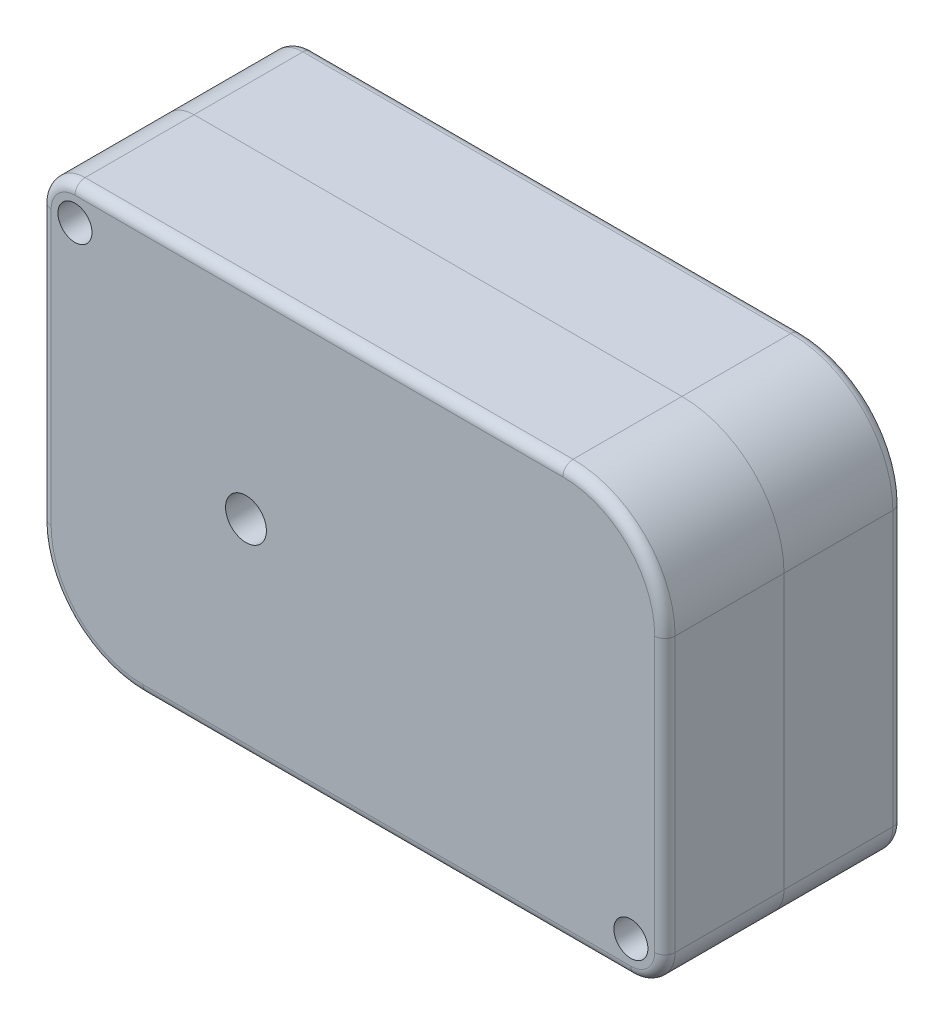
SolidWorks part; units mm, degrees
ref_plane "Front Plane" through (0, 0, 0) normal (0, 0, 1) x (1, 0, 0)
ref_plane "Top Plane" through (0, 0, 0) normal (0, 1, 0) x (1, 0, 0)
ref_plane "Right Plane" through (0, 0, 0) normal (1, 0, 0) x (0, 0, -1)
sketch "Sketch1" plane through (0, 0, 0) normal (0, 0, 1) x (1, 0, 0)
  line L0 (-91.0423, 53.272) -> (28.1923, 53.272)
  line L1 (-113.122, 60.272) -> (30.272, 60.272)
  line L2 (-123.122, 50.272) -> (-123.122, -30.272)
  line L3 (-93.122, -60.272) -> (50.272, -60.272)
  line L4 (60.272, 30.272) -> (60.272, -50.272)
  line L5 (-91.0423, -53.272) -> (28.1923, -53.272)
  line L6 (-116.122, -28.1923) -> (-116.122, 28.1923)
  line L7 (53.272, -28.1923) -> (53.272, 28.1923)
  arc A1 (-31.425, -39.2396) -> (-31.425, 39.2396) centre (0, 0) ccw
  arc A5 (-15.0759, 15.6496) -> (-15.0759, -15.6496) centre (-62.85, 0) ccw
  arc A6 (-62.85, 60.272) -> (-62.85, -60.272) centre (-62.85, 0) ccw
  arc A7 (0, -60.272) -> (0, 60.272) centre (0, 0) ccw
  arc A8 (50.272, -60.272) -> (60.272, -50.272) centre (50.272, -50.272) ccw
  arc A11 (-113.122, 60.272) -> (-123.122, 50.272) centre (-113.122, 50.272) ccw
  arc A12 (-12.6047, 17.7007) -> (-12.6047, -17.7007) centre (-62.85, 0) ccw
  arc A13 (-31.425, -43.016) -> (-31.425, 43.016) centre (0, 0) ccw
  arc A14 (-31.425, 51.4313) -> (-31.425, -51.4313) centre (-62.85, 0) ccw construction
  arc A15 (-31.425, -51.4313) -> (-31.425, 51.4313) centre (0, 0) ccw construction
  arc A16 (30.272, 60.272) -> (60.272, 30.272) centre (30.272, 30.272) cw
  arc A17 (-123.122, -30.272) -> (-93.122, -60.272) centre (-93.122, -30.272) ccw
  circle A18 centre (-113.122, 50.272) radius 5
  circle A19 centre (50.272, -50.272) radius 5
  circle A20 centre (0, 0) radius 15.73
  circle A21 centre (0, 0) radius 21.73
  arc A22 (-31.425, 39.2396) -> (-31.425, -39.2396) centre (-62.85, 0) ccw construction
  arc A23 (-31.425, 43.016) -> (-31.425, -43.016) centre (-62.85, 0) ccw construction
  point P5 (0, 0)
  point P6 (0, 0)
  point P40 (53.272, 0)
  point P50 (-116.122, 0)
  dimension "D3" = 100.544
  dimension "D1" = 100.544
  dimension "D5" = 10
  dimension "D6" = 10
  dimension "D8" = 30
  dimension "D9" = 10
  dimension "D10" = 10
  dimension "D11" = 31.46
  dimension "D2" = 62.85
  dimension "D12" = 6
  dimension "D4" = 10
  dimension "D7" = 3
extrude "Boss-Extrude1" add sketch "Sketch1" along normal blind 25 contours L1 A11 L2 A6 A18 | A16 L1 A7 L4 | L3 A8 L4 A7 A19 | L2 A17 L3 A6 | L0 A7 L1 A6 | L3 A7 L5 A6 | L6 A6 | A7 L7 region at (-31.425, 56.5135, 0) region at (-108.9044, 46.0544, 0) region at (-118.9364, 0, 0) region at (44.5822, 44.5822, 0) region at (-107.4322, -44.5822, 0) region at (56.0864, 0, 0) region at (-31.425, -56.5135, 0) region at (46.0544, -46.0544, 0)
extrude "Boss-Extrude5" add sketch "Sketch1<5>" along normal blind 15 contours A21 A12 A1 | A13 A12 A1 | A13 L0 A12 | A13 L7 A7 L0 | A13 L5 A7 L7 | A13 A12 L5 | A12 L6 A6 L5 | A12 L0 A6 L6 region at (-101.133, 38.283, 0) region at (-31.425, 50.2536, 0) region at (38.283, 38.283, 0) region at (36.7066, 36.7066, 0) region at (-101.133, -38.283, 0) region at (38.283, -38.283, 0) region at (48.9919, 0, 0) region at (-31.425, -50.2536, 0)
sketch "Sketch1<5>" plane through (0, 0, 0) normal (0, 0, 1) x (1, 0, 0) same geometry as "Sketch1"
extrude "Boss-Extrude2" add sketch "Sketch1<3>" against normal blind 10 contours L1 A11 L2 A6 A18 | L0 A7 L1 A6 | A12 L0 A6 L6 | L6 A6 | A12 L6 A6 L5 | L2 A17 L3 A6 | A1 A12 A5 | A21 A5 | L3 A7 L5 A6 | A13 A12 L5 | A21 A5 A1 A12 | A20 | A21 A12 A1 A5 | A21 A20 | A21 A12 A1 | A13 A12 A1 | A13 L0 A12 | A13 L7 A7 L0 | A16 L1 A7 L4 | A7 L7 | L3 A8 L4 A7 A19 | A13 L5 A7 L7 region at (-31.425, 56.5135, 0) region at (-108.9044, 46.0544, 0) region at (-101.133, 38.283, 0) region at (-31.425, 50.2536, 0) region at (-46.749, 49.3345, 0) region at (-118.9364, 0, 0) region at (38.283, 38.283, 0) region at (36.7066, 36.7066, 0) region at (-101.133, -38.283, 0) region at (44.5822, 44.5822, 0) region at (-107.4322, -44.5822, 0) region at (56.0864, 0, 0) region at (38.283, -38.283, 0) region at (-20.9278, 29.2135, 0) region at (48.9919, 0, 0) region at (-31.425, -56.5135, 0) region at (-31.425, -50.2536, 0) region at (46.0544, -46.0544, 0) region at (-20.9278, -29.2135, 0) region at (-64.0167, 0, 0) region at (9.6756, 18.7681, 0) region at (0, 0, 0)
sketch "Sketch1<3>" plane through (0, 0, 0) normal (0, 0, 1) x (1, 0, 0) same geometry as "Sketch1"
fillet "Fillet1" radius 3 8 edges at (-21.425, -60.272, -10) (57.3431, -57.3431, -10) (60.272, -10, -10) (51.4852, 51.4852, -10) (-41.425, 60.272, -10) (-120.1931, 57.3431, -10) (-123.122, 10, -10) (-114.3352, -51.4852, -10)
ref_plane "Plane1" through (0, 0, 25) normal (0, 0, 1) x (1, 0, 0)
mirror "Mirror1" about plane through (0, 0, 25) normal (0, 0, 1) of bodies 115 109
sketch "Sketch2" plane through (0, 0, -10) normal (0, 0, -1) x (-1, 0, 0)
  circle A0 centre (62.85, 0) radius 6
  circle A1 centre (62.85, 0) radius 50
  dimension "D1" = 12
  dimension "D2" = 100
extrude "Boss-Extrude6" add sketch "Sketch2" along normal blind 5 contours A1 A0 region at (-14.2642, 0, -10)
extrude "Cut-Extrude1" cut sketch "Sketch2<3>" against normal through all contours A0 region at (-62.85, 0, -10)
sketch "Sketch2<3>" plane through (0, 0, -10) normal (0, 0, -1) x (-1, 0, 0) same geometry as "Sketch2"
sketch "Sketch3" plane through (0, 0, -15) normal (0, 0, -1) x (-1, 0, 0)
  circle A0 centre (62.85, 0) radius 35 construction
  circle A1 centre (62.85, 35) radius 2.5
  circle A2 centre (87.5987, 24.7487) radius 2.5
  circle A3 centre (97.85, 0) radius 2.5
  circle A4 centre (87.5987, -24.7487) radius 2.5
  circle A5 centre (62.85, -35) radius 2.5
  circle A6 centre (38.1013, -24.7487) radius 2.5
  circle A7 centre (27.85, 0) radius 2.5
  circle A8 centre (38.1013, 24.7487) radius 2.5
  point P21 (62.85, 0)
  dimension "D1" = 70
  dimension "D2" = 5
  dimension "D3" = 8
extrude "Cut-Extrude2" cut sketch "Sketch3" against normal blind 20
equation "\"D1@Sketch1\"=\"D3@Sketch1\""
